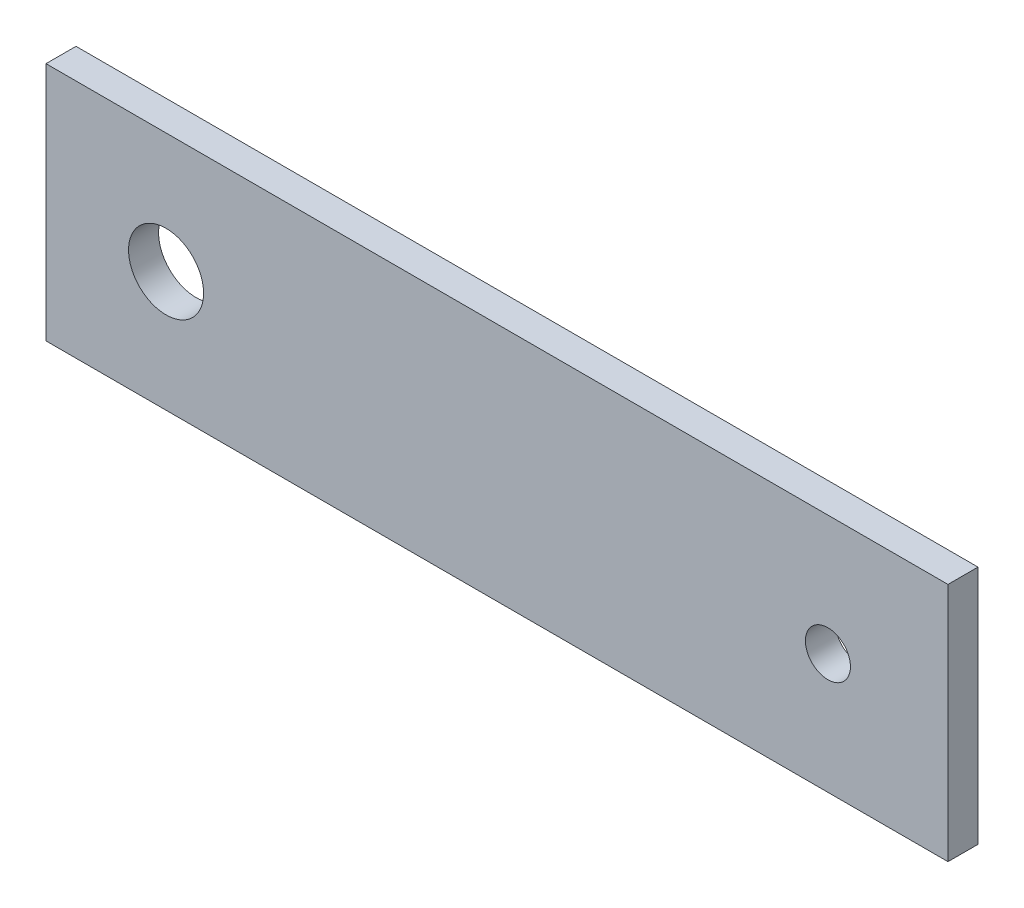
SolidWorks part; units mm, degrees
ref_plane "前视基准面" through (0, 0, 0) normal (0, 0, 1) x (1, 0, 0)
ref_plane "上视基准面" through (0, 0, 0) normal (0, 1, 0) x (1, 0, 0)
ref_plane "右视基准面" through (0, 0, 0) normal (1, 0, 0) x (0, 0, -1)
other "Configuration Table"
sketch "草图1" plane through (0, 0, 0) normal (0, 0, 1) x (1, 0, 0)
  line L1 (-16, -16) -> (104.2, -16)
  line L2 (-16, -16) -> (-16, 16)
  line L3 (-16, 16) -> (104.2, 16)
  line L4 (104.2, -16) -> (104.2, 16)
  line L5 (-16, -16) -> (104.2, 16) construction
  line L6 (-16, 16) -> (104.2, -16) construction
  circle A0 centre (0, 0) radius 5
  circle A1 centre (88.2, 0) radius 3
  point P0 (44.1, 0)
extrude "凸台-拉伸1" add sketch "草图1" along normal mid plane 4
